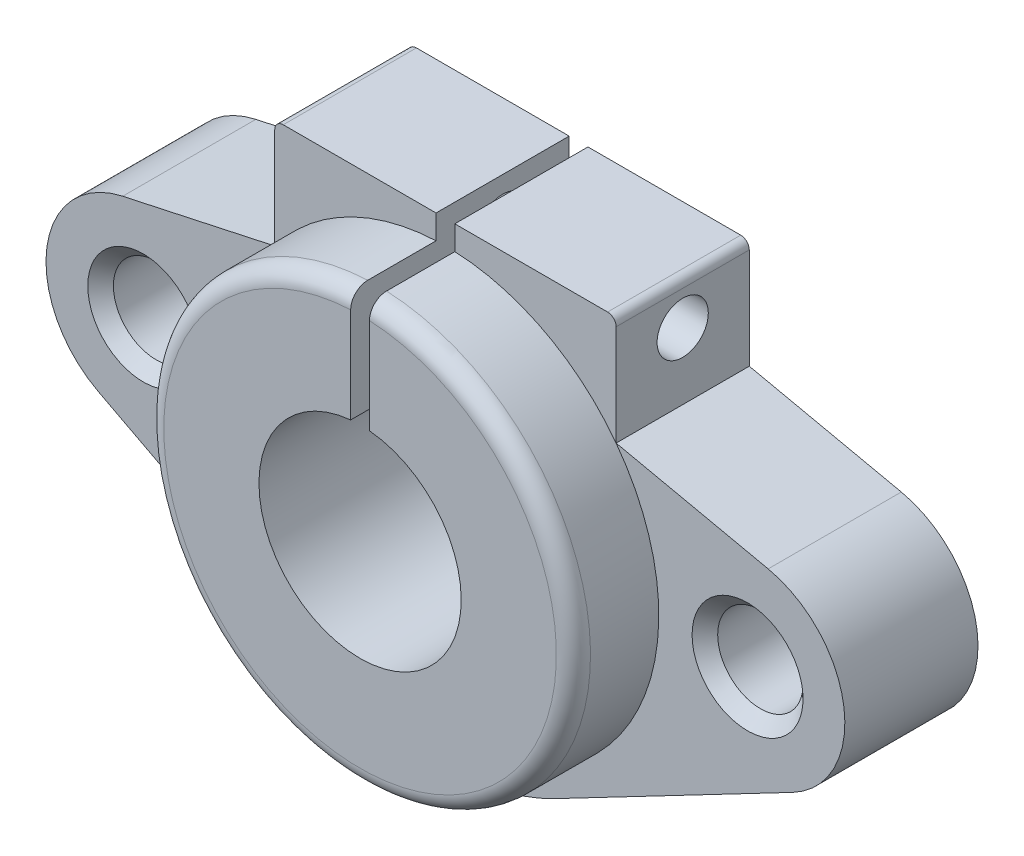
SolidWorks part; units mm, degrees
ref_plane "Alzado" through (0, 0, 0) normal (0, 0, 1) x (1, 0, 0)
ref_plane "Planta" through (0, 0, 0) normal (0, 1, 0) x (1, 0, 0)
ref_plane "Vista lateral" through (0, 0, 0) normal (1, 0, 0) x (0, 0, -1)
sketch "Croquis1" plane through (0, 0, 0) normal (0, 0, 1) x (1, 0, 0)
  circle A0 centre (0, 0) radius 12.5
  circle A1 centre (0, 0) radius 5.925
  dimension "D1" = 25
  dimension "D2" = 11.85
extrude "Saliente-Extruir1" add sketch "Croquis1" along normal blind 12.8
sketch "Croquis2" plane through (0, 0, 0) normal (0, 0, -1) x (-1, 0, 0)
  line L0 (-17.7, 0) -> (17.7, 0) construction
  line L1 (-6.4395, -12.3184) -> (-20.3407, -5.0514)
  line L2 (6.4395, -12.3184) -> (20.3407, -5.0514)
  line L3 (0, 0) -> (0, 13.9) construction
  line L4 (-10, 13.9) -> (10, 13.9)
  line L5 (-10, 13.9) -> (-10, 7.5)
  line L6 (10, 13.9) -> (10, 7.5)
  line L7 (-10, 7.5) -> (-18.9066, 5.5708)
  line L8 (10, 7.5) -> (18.9066, 5.5708)
  circle A0 centre (0, 0) radius 13.9 construction
  circle A1 centre (-17.7, 0) radius 5.7 construction
  circle A2 centre (17.7, 0) radius 5.7 construction
  arc A3 (-6.4395, -12.3184) -> (6.4395, -12.3184) centre (0, 0) ccw
  circle A4 centre (0, 0) radius 12.5 construction
  arc A5 (-20.3407, -5.0514) -> (-18.9066, 5.5708) centre (-17.7, 0) cw
  arc A6 (18.9066, 5.5708) -> (20.3407, -5.0514) centre (17.7, 0) cw
  circle A7 centre (0, 0) radius 12.5 construction
  circle A8 centre (0, 0) radius 5.925 construction
  circle A9 centre (0, 0) radius 5.925
  point P4 (0, 0)
  point P15 (-18.9066, 5.5708)
  point P19 (0, 13.9)
  point P25 (-10, 7.5)
  point P26 (-20.3407, -5.0514)
  point P27 (6.4395, -12.3184)
  point P28 (-6.4395, -12.3184)
  point P29 (0, 0)
  dimension "D2" = 27.8
  dimension "D3" = 11.4
  dimension "D4" = 11.4
  dimension "D1" = 35.4
  dimension "D5" = 20
extrude "Saliente-Extruir2" add sketch "Croquis2" against normal blind 7.8
sketch "Croquis3" plane through (0, 0, 0) normal (0, 0, -1) x (-1, 0, 0)
  circle A0 centre (-17.7, 0) radius 2.5
  circle A1 centre (17.7, 0) radius 2.5
  point P0 (-17.7, 0)
  point P1 (17.7, 0)
  dimension "D1" = 5
extrude "Cortar-Extruir1" cut sketch "Croquis3" against normal up to vertex (7.8 mm away) up to point (-10, 7.5, 7.8)
sketch "Croquis4" plane through (0, 0, 0) normal (0, 0, -1) x (-1, 0, 0)
  line L0 (0, 0) -> (0, 13.9) construction
  line L1 (10, 13.9) -> (-10, 13.9) construction
  line L2 (-0.55, 13.9) -> (0.55, 13.9)
  line L3 (0.55, 13.9) -> (0.55, 5.8994)
  line L4 (-0.55, 13.9) -> (-0.55, 5.8994)
  circle A0 centre (0, 0) radius 5.925 construction
  circle A1 centre (0, 0) radius 5.925 construction
  arc A2 (-0.55, 5.8994) -> (0.5766, 5.8969) centre (0, 0) cw
  point P10 (0, 13.9)
  line M7 (10, 13.9) -> (-10, 13.9)
  circle M15 centre (0, 0) radius 5.925
  dimension "D1" = 1.1
extrude "Cortar-Extruir2" cut sketch "Croquis4" against normal blind 13 contours L4 L3 M7 M15 region at (0, 9.9082, 0)
fillet "Redondeo1" radius 1 1 edges at (0, -12.5, 12.8)
sketch "Croquis5" plane through (10, 0, 0) normal (1, 0, 0) x (0, 0, -1)
  line L0 (-7.8, 11.4) -> (0, 11.4) construction
  line L1 (-7.8, 13.9) -> (-7.8, 7.5) construction
  line L2 (0, 13.9) -> (0, 7.5) construction
  line L3 (-7.8, 13.9) -> (0, 13.9) construction
  circle A0 centre (-3.9, 11.4) radius 1.5
  dimension "D1" = 3
  dimension "D2" = 2.5
extrude "Cortar-Extruir3" cut sketch "Croquis5" against normal up to vertex (20 mm away) up to point (-10, 13.9, 7.8)
fillet "Redondeo2" radius 0.5 2 edges at (-10, 13.9, 3.9) (10, 13.9, 3.9)
chamfer "Chaflán1" distance 0.75 angle 45 2 edges at (-20.2, 0, 7.8) (15.2, 0, 7.8)
equation "\"D4@Croquis2\"=\"D3@Croquis2\""
